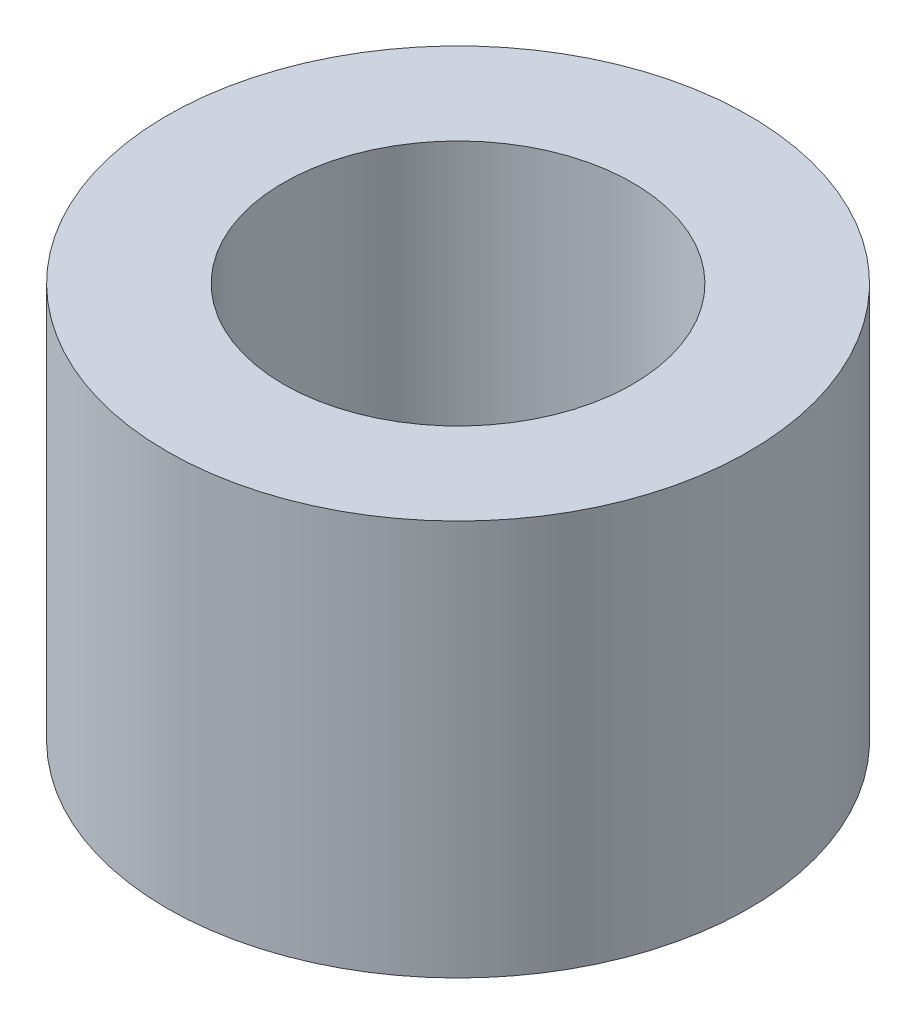
SolidWorks part; units mm, degrees
ref_plane "Front Plane" through (0, 0, 0) normal (0, 0, 1) x (1, 0, 0)
ref_plane "Top Plane" through (0, 0, 0) normal (0, 1, 0) x (1, 0, 0)
ref_plane "Right Plane" through (0, 0, 0) normal (1, 0, 0) x (0, 0, -1)
sketch "Sketch1" plane through (0, 0, 0) normal (0, 1, 0) x (1, 0, 0)
  circle A0 centre (0, 0) radius 1.5
  circle A1 centre (0, 0) radius 2.5
  dimension "D1" = 3
  dimension "D2" = 5
extrude "Boss-Extrude1" add sketch "Sketch1" along normal blind 3.4
